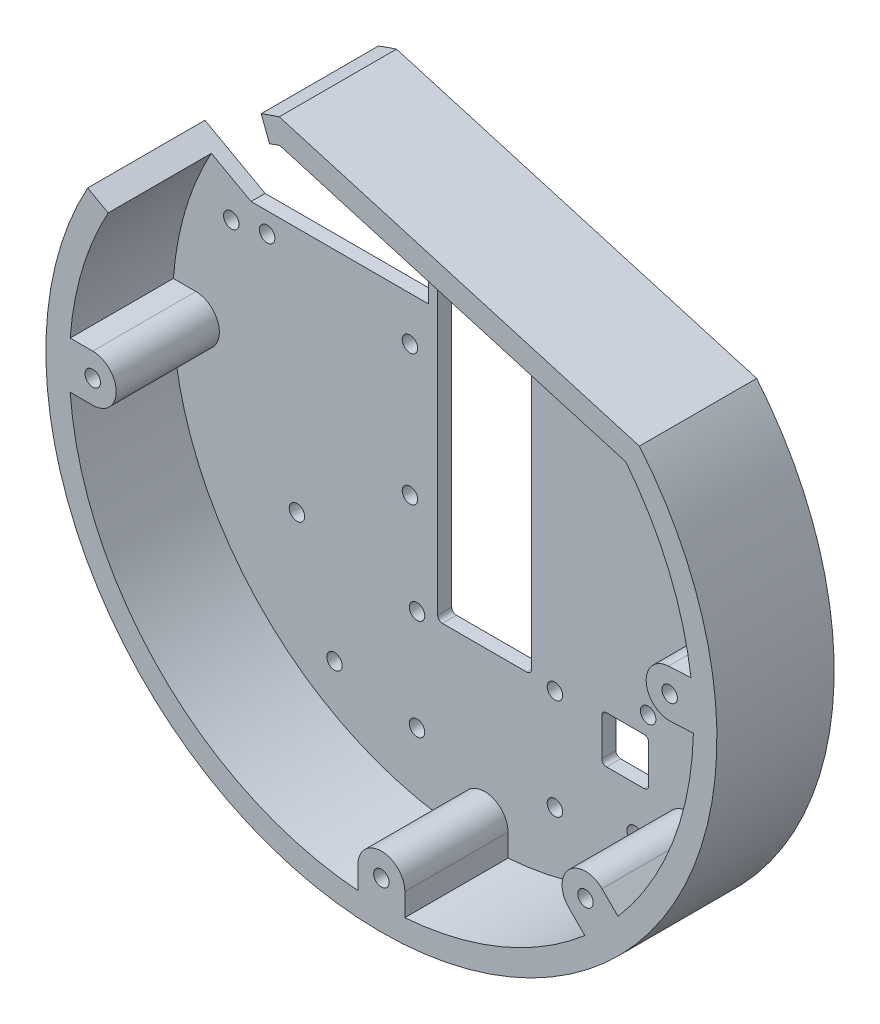
SolidWorks part; units mm, degrees
ref_plane "Front Plane" through (0, 0, 0) normal (1, 0, 0) x (0, 1, 0)
ref_plane "Top Plane" through (0, 0, 0) normal (0, 0, 1) x (0, 1, 0)
ref_plane "Right Plane" through (0, 0, 0) normal (0, 1, 0) x (-1, 0, 0)
sketch "Sketch1" plane through (0, 0, 0) normal (0, 0, 1) x (0, 1, 0)
  circle A0 centre (0, 0) radius 71.545
  circle A1 centre (-48.5, 32) radius 1.65
  circle A2 centre (22, 54) radius 1.65
  circle A3 centre (24, -52) radius 1.65
  circle A4 centre (-48.5, -32) radius 1.65
  dimension "D1" = 143.09
  dimension "D2" = 48.5
  dimension "D8" = 52
  dimension "D9" = 3.3
  dimension "D3" = 32
  dimension "D4" = 24
  dimension "D5" = 22
  dimension "D6" = 54
  dimension "D7" = 32
  dimension "D10" = 48.5
extrude "Plate extrud" add sketch "Sketch1" along normal blind 3
sketch "Sketch2" plane through (0, 0, 0) normal (0, 0, 1) x (0, 1, 0)
  line L0 (-27.54, -50.11) -> (25.76, -50.11) construction
  line L1 (-18.54, -56.91) -> (-6.54, -56.91) construction
  circle A0 centre (-25, 40) radius 1.65
  circle A1 centre (23.22, 46.36) radius 1.65
  circle A2 centre (18.14, 15.91) radius 1.65
  circle A3 centre (-9.77, 15.91) radius 1.65
  circle A4 centre (-25, -34.88) radius 1.65
  circle A5 centre (23.22, -36.11) radius 1.65
  dimension "D1" = 3.3
  dimension "D2" = 6.36
  dimension "D3" = 24.09
  dimension "D4" = 74.88
  dimension "D5" = 76.11
  dimension "D6" = 15.23
  dimension "D7" = 43.14
  dimension "D8" = 48.22
  dimension "D9" = 2.54
  dimension "D12" = 6.46
  dimension "D15" = 40
  dimension "D10" = 50.76
  dimension "D11" = 90.11
  dimension "D13" = 18.46
  dimension "D14" = 96.91
  dimension "D16" = 25
extrude "Arduino mount holes" cut sketch "Sketch2" along normal blind 3
sketch "Sketch4" plane through (0, 0, 0) normal (0, 0, 1) x (0, 1, 0)
  line L5 (-29, 10) -> (49, 10)
  line L6 (-30, 9) -> (-30, -9)
  line L7 (-29, -10) -> (49, -10)
  line L8 (50, 9) -> (50, -9)
  line L9 (-38, -25) -> (-30, -25)
  line L10 (-39, -26) -> (-39, -34)
  line L11 (-38, -35) -> (-30, -35)
  line L12 (-29, -26) -> (-29, -34)
  line L13 (-39, -25) -> (-29, -35) construction
  line L14 (-39, -35) -> (-29, -25) construction
  arc A4 (-30, -9) -> (-29, -10) centre (-29, -9) ccw
  arc A5 (-29, 10) -> (-30, 9) centre (-29, 9) ccw
  arc A6 (49, 10) -> (50, 9) centre (49, 9) cw
  arc A7 (49, -10) -> (50, -9) centre (49, -9) ccw
  arc A8 (-30, -35) -> (-29, -34) centre (-30, -34) ccw
  arc A9 (-30, -25) -> (-29, -26) centre (-30, -26) cw
  arc A10 (-38, -25) -> (-39, -26) centre (-38, -26) ccw
  arc A11 (-39, -34) -> (-38, -35) centre (-38, -34) ccw
  point P0 (0, 0)
  point P1 (-34, -30)
  point P10 (-30, -10)
  point P15 (50, 10)
  point P18 (50, -10)
  dimension "D3" = 10
  dimension "D5" = 1
  dimension "D10" = 1
  dimension "D1" = 80
  dimension "D2" = 20
  dimension "D4" = 30
  dimension "D6" = 34
  dimension "D7" = 30
  dimension "D8" = 10
  dimension "D9" = 10
extrude "Cable hole" cut sketch "Sketch4" along normal through all contours L8 A7 L7 A4 L6 A5 L5 A6 | L10 A11 L11 A8 L12 A9 L9 A10
sketch "Sketch5" plane through (0, 0, 0) normal (0, 0, 1) x (0, 1, 0)
  circle A0 centre (-52, -15) radius 1.65
  circle A1 centre (-30.5, -15) radius 1.65
  circle A2 centre (-30.5, 14.4) radius 1.65
  circle A3 centre (-52, 14.4) radius 1.65
  dimension "D1" = 3.3
  dimension "D2" = 15
  dimension "D3" = 21.5
  dimension "D4" = 29.4
  dimension "D5" = 21.5
  dimension "D6" = 52
extrude "Relay mount holes" cut sketch "Sketch5" along normal through all
sketch "Sketch6" plane through (0, 0, 0) normal (0, 0, 1) x (0, 1, 0)
  line L0 (3.221, -61.4607) -> (0, 0) construction
  line L1 (-66.545, 0) -> (66.545, 0) construction
  line L2 (0, 66.545) -> (0, -66.545) construction
  line L3 (-47.0544, -47.0544) -> (47.0544, 47.0544) construction
  line L4 (-66.545, 0) -> (66.545, 0) construction
  line L5 (-66.3569, 5) -> (-61.545, 5)
  line L6 (-61.545, -5) -> (-66.3569, -5)
  line L7 (5, 66.3569) -> (5, 61.545)
  line L8 (-5, 61.545) -> (-5, 66.3569)
  line L9 (-1.5203, -66.5276) -> (-1.7721, -61.7223)
  line L10 (8.2142, -61.199) -> (8.466, -66.0043)
  line L11 (-50.4569, -43.3859) -> (-47.0544, -39.9834)
  line L12 (-39.9834, -47.0544) -> (-43.3859, -50.4569)
  line L13 (45.7364, -55.017) -> (68.1495, 21.7792)
  line L14 (62.9131, 21.6837) -> (41.3733, -52.1199)
  arc A0 (68.4188, 20.9177) -> (45.7364, -55.017) centre (0, 0) ccw
  arc A1 (-66.3569, -5) -> (41.3733, -52.1199) centre (0, 0) ccw
  arc A2 (-61.545, 5) -> (-61.545, -5) centre (-61.545, 0) cw
  arc A3 (68.4188, 20.9177) -> (45.7364, -55.017) centre (0, 0) ccw
  circle A4 centre (-61.545, 0) radius 1.65
  arc A5 (-66.3569, -5) -> (-66.3569, 5) centre (0, 0) cw
  arc A7 (5, 61.545) -> (-5, 61.545) centre (0, 61.545) cw
  circle A8 centre (0, 61.545) radius 1.65
  arc A9 (8.466, -66.0043) -> (-1.5203, -66.5276) centre (0, 0) cw
  arc A10 (-1.7721, -61.7223) -> (8.2142, -61.199) centre (3.221, -61.4607) cw
  circle A11 centre (3.221, -61.4607) radius 1.65
  arc A12 (-43.3859, -50.4569) -> (-50.4569, -43.3859) centre (0, 0) cw
  arc A13 (-47.0544, -39.9834) -> (-39.9834, -47.0544) centre (-43.5189, -43.5189) cw
  circle A14 centre (-43.5189, -43.5189) radius 1.65
  arc A15 (62.9131, 21.6837) -> (5, 66.3569) centre (0, 0) ccw
  arc A17 (-5, 66.3569) -> (-66.3569, 5) centre (0, 0) ccw
  point P12 (0, 0)
  point P16 (0, 0)
  point P47 (0, 0)
  dimension "D1" = 5
  dimension "D2" = 143.09
  dimension "D3" = 45
  dimension "D8" = 3.3
  dimension "D9" = 61.545
  dimension "D10" = 3.3
  dimension "D11" = 5
  dimension "D17" = 5
  dimension "D18" = 3.3
  dimension "D5" = 5
  dimension "D6" = 5
  dimension "D7" = 5
  dimension "D12" = 3
  dimension "D13" = 80
  dimension "D14" = 16.27
  dimension "D15" = 5
  dimension "D16" = 10
  dimension "D20" = 4.8119
extrude "Boss-Extrude3" add sketch "Sketch6" along normal blind 25 contours L13 A0 A15 L14 A1 A5 | A13 L11 A1 L12 A14 | A10 L9 A1 L10 A11 | A5 L6 A2 L5 A4 | A7 L7 L8 A8 region at (-4.8586, -63.9509, 0) region at (41.804, -48.6363, 0) region at (64.1175, -1.5027, 0) region at (-19.4841, -66.7601, 0)
sketch "Sketch7" plane through (0, 0, 25) normal (0, 0, 1) x (1, 0, 0)
  line L0 (55.017, 45.7364) -> (-21.7792, 68.1495) construction
  line L1 (-21.7792, 68.1495) -> (55.017, 45.7364)
  arc A0 (-21.7792, 68.1495) -> (55.017, 45.7364) centre (0, 0) cw
extrude "Cut-Extrude1" cut sketch "Sketch7" against normal through all
sketch "Sketch8" plane through (0, 0, 0) normal (0, 0, 1) x (0, 1, 0)
  line L1 (-60.1543, 2.8547) -> (-63.3219, 2.6318)
  line L2 (-63.3219, 2.6318) -> (-64.7126, -0.2229)
  line L3 (-64.7126, -0.2229) -> (-62.9357, -2.8547)
  line L4 (-62.9357, -2.8547) -> (-59.7681, -2.6318)
  line L5 (-59.7681, -2.6318) -> (-58.3774, 0.2229)
  line L6 (-58.3774, 0.2229) -> (-60.1543, 2.8547)
  line L7 (2.9623, 60.4014) -> (2.4716, 63.5387)
  line L8 (2.4716, 63.5387) -> (-0.4908, 64.6823)
  line L9 (-0.4908, 64.6823) -> (-2.9623, 62.6886)
  line L10 (-2.9623, 62.6886) -> (-2.4716, 59.5513)
  line L11 (-2.4716, 59.5513) -> (0.4908, 58.4077)
  line L12 (0.4908, 58.4077) -> (2.9623, 60.4014)
  line L13 (6.3964, -61.4607) -> (4.8087, -58.7107)
  line L14 (4.8087, -58.7107) -> (1.6333, -58.7107)
  line L15 (1.6333, -58.7107) -> (0.0456, -61.4607)
  line L16 (0.0456, -61.4607) -> (1.6333, -64.2107)
  line L17 (1.6333, -64.2107) -> (4.8087, -64.2107)
  line L18 (4.8087, -64.2107) -> (6.3964, -61.4607)
  line L19 (-40.3435, -43.5189) -> (-41.9312, -40.7689)
  line L20 (-41.9312, -40.7689) -> (-45.1066, -40.7689)
  line L21 (-45.1066, -40.7689) -> (-46.6943, -43.5189)
  line L22 (-46.6943, -43.5189) -> (-45.1066, -46.2689)
  line L23 (-45.1066, -46.2689) -> (-41.9312, -46.2689)
  line L24 (-41.9312, -46.2689) -> (-40.3435, -43.5189)
  circle A0 centre (-61.545, 0) radius 2.75 construction
  circle A1 centre (0, 61.545) radius 2.75 construction
  circle A2 centre (3.221, -61.4607) radius 2.75 construction
  circle A3 centre (-43.5189, -43.5189) radius 2.75 construction
  dimension "D1" = 5.5
extrude "Cut-Extrude2" cut sketch "Sketch8" against normal blind 2.6 from offset 22
sketch "Sketch9" plane through (0, 0, 0) normal (0, 0, 1) x (0, 1, 0)
  line L0 (0, 0) -> (50000, 0) construction
  line L1 (66.793, 25.6394) -> (50, 19.1932)
  line L2 (34.5874, 62.6291) -> (27.5, 49.7956)
  line L3 (0, 0) -> (27.5, 49.7956) construction
  line L4 (0, 0) -> (50, 19.1932) construction
  line L5 (50, 19.1932) -> (50, 12)
  line L6 (50, 12) -> (27.5, 12)
  line L7 (27.5, 12) -> (27.5, 49.7956)
  line L9 (50, 9) -> (50, -9) construction
  arc A0 (66.793, 25.6394) -> (34.5874, 62.6291) centre (0, 0) ccw
  arc A1 (68.1495, 21.7792) -> (45.7364, -55.017) centre (0, 0) ccw construction
  dimension "D1" = 21
  dimension "D2" = 40.09
  dimension "D3" = 22.5
  dimension "D4" = 12
extrude "Cut-Extrude3" cut sketch "Sketch9" along normal through all
ref_plane "Plane1" through (0, 0, 0) normal (-0.7071, 0.7071, 0) x (0.7071, 0.7071, 0)
sketch "Sketch10" plane through (0, 0, 0) normal (-0.7071, 0.7071, 0) x (0.7071, 0.7071, 0)
  line L0 (-67.545, 0) -> (-76.045, 0)
  line L1 (71.2434, 0) -> (-71.545, 0) construction
  line L2 (-76.045, -10) -> (-67.545, -10)
  line L3 (-67.545, -10) -> (-67.545, 0)
  line L4 (-77.045, -9) -> (-77.045, -1)
  line L5 (-71.545, 0) -> (-71.545, -25) construction
  line L6 (-74.045, -2.5) -> (-74.045, -7.5) construction
  line L9 (-72.545, -2.5) -> (-72.545, -7.5)
  line L10 (-75.545, -2.5) -> (-75.545, -7.5)
  arc A1 (-76.045, 0) -> (-77.045, -1) centre (-76.045, -1) ccw
  arc A2 (-76.045, -10) -> (-77.045, -9) centre (-76.045, -9) cw
  arc A5 (-72.545, -2.5) -> (-75.545, -2.5) centre (-74.045, -2.5) ccw
  arc A6 (-75.545, -7.5) -> (-72.545, -7.5) centre (-74.045, -7.5) ccw
  point P13 (-74.045, -5)
  point P20 (-77.045, -5)
  dimension "D1" = 1
  dimension "D7" = 1.5
  dimension "D2" = 10
  dimension "D3" = 8.5
  dimension "D4" = 4
  dimension "D5" = 5
  dimension "D6" = 6.5
extrude "Boss-Extrude4" add sketch "Sketch10" along normal blind 10 and the other way blind 10
sketch "Sketch11" plane through (0, 0, 0) normal (0, 0, 1) x (0, 1, 0)
  line L0 (-54.6544, 46.1691) -> (-58.7217, 50.2364)
  line L1 (-61.5501, 47.408) -> (-47.408, 61.5501) construction
  line L2 (-58.7217, 50.2364) -> (-50.2364, 58.7217)
  line L3 (-50.2364, 58.7217) -> (-46.1691, 54.6544)
  line L4 (0, 0) -> (0, 50000) construction
  line L5 (0, 0) -> (-54.479, 54.479) construction
  arc A0 (-54.6544, 46.1691) -> (-46.1691, 54.6544) centre (0, 0) cw
  arc A1 (34.5874, 62.6291) -> (45.7364, -55.017) centre (0, 0) ccw construction
  point P16 (-54.479, 54.479)
  dimension "D1" = 12
  dimension "D2" = 45
extrude "Cut-Extrude4" cut sketch "Sketch11" along normal through all
sketch "Sketch12" plane through (0, 0, 0) normal (0, 0, 1) x (0, 1, 0)
  line L0 (30.82, -29.5) -> (40.18, -29.5) construction
  line L1 (28.9, -45.05) -> (42.1, -45.05) construction
  line L2 (28.9, -45.05) -> (28.9, -13.95) construction
  line L3 (28.9, -13.95) -> (42.1, -13.95) construction
  line L4 (42.1, -45.05) -> (42.1, -13.95) construction
  line L5 (28.9, -45.05) -> (42.1, -13.95) construction
  line L6 (28.9, -13.95) -> (42.1, -45.05) construction
  circle A0 centre (30.82, -29.5) radius 1.65
  circle A1 centre (40.18, -29.5) radius 1.65
  point P0 (35.5, -29.5)
  point P9 (35.5, -29.5)
  dimension "D6" = 3.3
  dimension "D1" = 31.1
  dimension "D2" = 13.2
  dimension "D3" = 29.5
  dimension "D4" = 35.5
  dimension "D5" = 9.36
extrude "Cut-Extrude5" cut sketch "Sketch12" along normal through all
